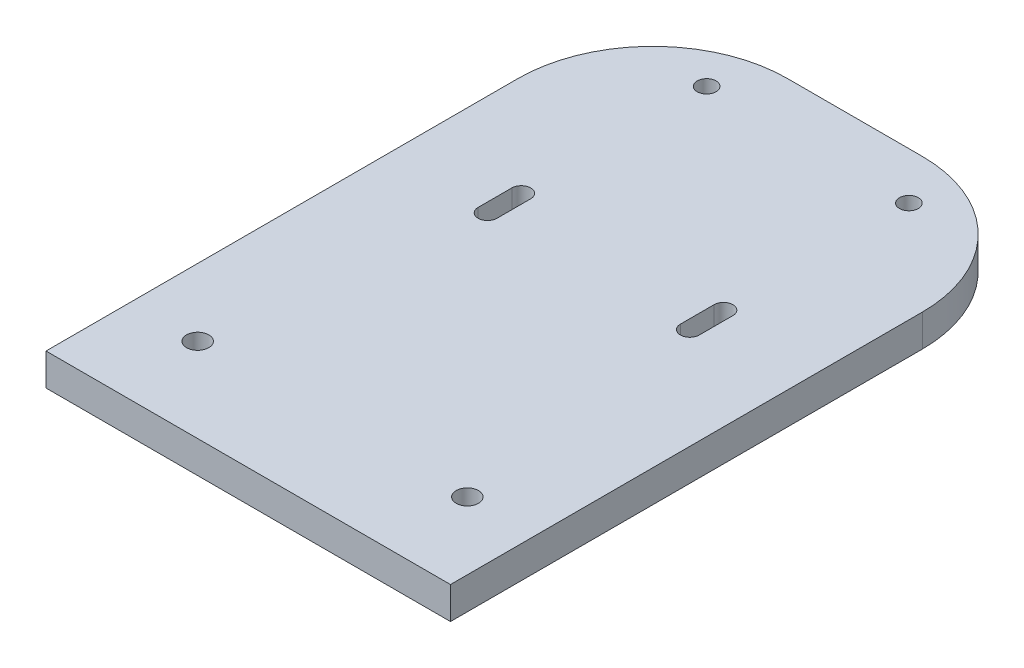
SolidWorks part; units mm, degrees
ref_plane "Front Plane" through (0, 0, 0) normal (0, 0, 1) x (1, 0, 0)
ref_plane "Top Plane" through (0, 0, 0) normal (0, 1, 0) x (1, 0, 0)
ref_plane "Right Plane" through (0, 0, 0) normal (1, 0, 0) x (0, 0, -1)
sketch "Sketch1" plane through (0, 0, 0) normal (0, 1, 0) x (1, 0, 0)
  line L1 (0, 0) -> (60, 0)
  line L2 (0, 0) -> (0, 90)
  line L3 (0, 90) -> (60, 90)
  line L4 (60, 0) -> (60, 90)
  dimension "D1" = 90
  dimension "D2" = 60
extrude "Boss-Extrude1" add sketch "Sketch1" along normal blind 4.76
sketch "Sketch2" plane through (0, 4.76, 0) normal (0, 1, 0) x (1, 0, 0)
  line L0 (0, 12.5) -> (60, 12.5) construction
  line L1 (0, 90) -> (0, 0) construction
  line L2 (60, 0) -> (60, 90) construction
  line L3 (0, 0) -> (60, 0) construction
  line L4 (30, 90) -> (30, 0) construction
  line L5 (60, 90) -> (0, 90) construction
  line L6 (0, 24.3727) -> (0, 25) construction
  line L7 (0, 25) -> (60, 25) construction
  line L8 (0, 68) -> (60, 68) construction
  line L9 (15, 55.5) -> (15, 50.5) construction
  line L10 (16.4, 55.5) -> (16.4, 50.5)
  line L11 (13.6, 55.5) -> (13.6, 50.5)
  line L12 (45, 55.5) -> (45, 50.5) construction
  line L13 (43.6, 55.5) -> (43.6, 50.5)
  line L14 (46.4, 55.5) -> (46.4, 50.5)
  circle A0 centre (10, 12.5) radius 1.65
  circle A1 centre (50, 12.5) radius 1.65
  circle A2 centre (15, 83) radius 1.4
  circle A3 centre (45, 83) radius 1.4
  arc A4 (16.4, 55.5) -> (13.6, 55.5) centre (15, 55.5) ccw
  arc A5 (13.6, 50.5) -> (16.4, 50.5) centre (15, 50.5) ccw
  arc A6 (43.6, 55.5) -> (46.4, 55.5) centre (45, 55.5) cw
  arc A7 (46.4, 50.5) -> (43.6, 50.5) centre (45, 50.5) cw
  point P27 (15, 53)
  point P34 (45, 53)
  dimension "D2" = 3.3
  dimension "D6" = 2.8
  dimension "D9" = 1.4
  dimension "D1" = 12.5
  dimension "D3" = 20
  dimension "D4" = 12.5
  dimension "D5" = 22
  dimension "D7" = 15
  dimension "D8" = 15
  dimension "D10" = 5
  dimension "D11" = 15
extrude "Cut-Extrude1" cut sketch "Sketch2" against normal through all
fillet "Fillet1" radius 20 2 edges at (60, 2.38, -90) (0, 2.38, -90)
equation "\"Change based on what software wants\"= 90"
equation "\"D1@Sketch1\"= \"Change based on what software wants\""
